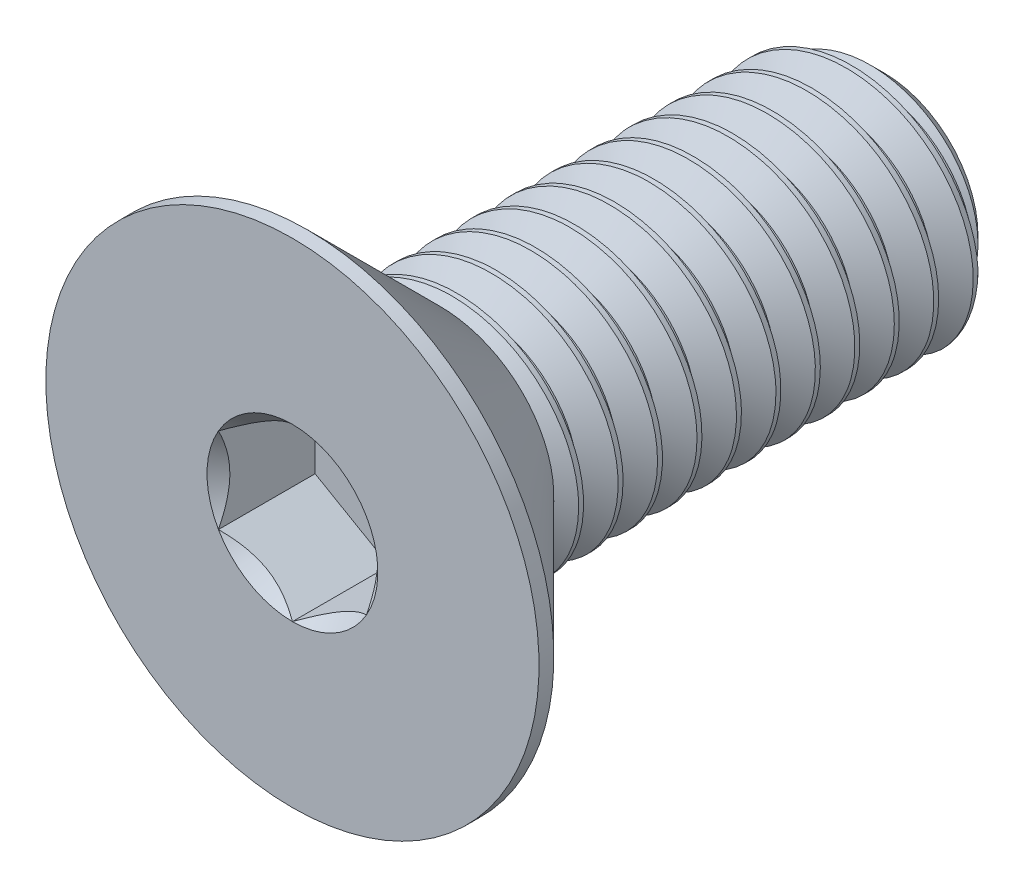
SolidWorks part; units mm, degrees
ref_plane "Front" through (0, 0, 0) normal (0, 0, 1) x (1, 0, 0)
ref_plane "Top" through (0, 0, 0) normal (0, 1, 0) x (1, 0, 0)
ref_plane "Right" through (0, 0, 0) normal (1, 0, 0) x (0, 0, -1)
sketch "Body Sketch" plane through (0, 0, 0) normal (1, 0, 0) x (0, 0, -1)
  line L0 (0, 5) -> (0.3, 5) construction
  line L1 (0.3, 5) -> (2.8, 2.5) construction
  line L2 (0, 2.5) -> (12, 2.5)
  line L3 (12, 2.5) -> (12, 0)
  line L4 (12, 0) -> (0, 0)
  line L5 (0, 0) -> (0, 5) construction
  line L6 (0, 5) -> (0, -5) construction
  line L7 (12, 2.5) -> (12, -2.5) construction
  line L8 (0, -5) -> (0.3, -5) construction
  line L9 (0.3, -5) -> (2.8, -2.5) construction
  line L11 (0, 2.5) -> (0, 0)
  line L12 (2.8, 2.5) -> (2.8, 0) construction
revolve "Body Revolve" add sketch "Body Sketch" angle 360 mid plane about L4
sketch "Thread Spiral Sketch" plane through (0, 0, -12) normal (0, 0, -1) x (-1, 0, 0)
  circle A0 centre (0, 0) radius 2.5
curve "Thread Spiral" pitch 0.8 height 12 radius 2.5 centre (0, 0, -12) axis (0, 0, 1) start towards (0, 1, 0)
sketch "Thread Cut Sketch" plane through (0, 0, 0) normal (1, 0, 0) x (0, 0, -1)
  line L0 (12, 2.5) -> (12.7, 2.5)
  line L1 (12.7, 2.5) -> (12.4, 1.9804)
  line L2 (12.4, 1.9804) -> (12.3, 1.9804)
  line L3 (12.3, 1.9804) -> (12, 2.5)
  line L4 (12.15, 2.2402) -> (12.55, 2.2402) construction
  dimension "D1" = 60
  dimension "D2" = 0.1
  dimension "D3" = 0.4
chamfer "Tip Chamfer" distance 0.6 angle 45 1 edges at (0, 2.5, -12)
sweep "Thread Cut" cut profiles "Thread Cut Sketch" path "Thread Spiral" align with end faces yes
sketch "Head Revolve Sketch" plane through (0, 0, 0) normal (1, 0, 0) x (0, 0, -1)
  line L0 (0, 5) -> (0.3, 5) construction
  line L1 (0.3, 5) -> (2.8, 2.5) construction
  line L2 (0, 5) -> (0.3, 5)
  line L3 (0.3, 5) -> (2.8, 2.5)
  line L4 (2.8, 2.5) -> (2.8, 0) construction
  line L5 (2.8, 2.5) -> (2.8, 0)
  line L7 (0, 0) -> (0, 5) construction
  line L8 (0, 0) -> (0, 5)
  line L9 (0, 0) -> (2.8, 0)
  line L10 (5.5, 0) -> (-5.5, 0) construction
revolve "Head Revolve" add sketch "Head Revolve Sketch" angle 360 mid plane about L9
ref_plane "Base of Head Plane" through (0, 0, -2.8) normal (0, 0, 1) x (1, 0, 0)
sketch "Head to Thread Merger Sketch" plane through (0, 0, -2.8) normal (0, 0, 1) x (1, 0, 0)
  circle A0 centre (0, 0) radius 2.5
extrude "Head to Thread Merger Extrude" add sketch "Head to Thread Merger Sketch" against normal through all draft 45
sketch "Hex Cut Sketch" plane through (0, 0, 0) normal (0, 0, 1) x (1, 0, 0)
  line L1 (1.5, -0.866) -> (1.5, 0.866)
  line L2 (1.5, 0.866) -> (0, 1.7321)
  line L3 (0, 1.7321) -> (-1.5, 0.866)
  line L4 (-1.5, 0.866) -> (-1.5, -0.866)
  line L5 (-1.5, -0.866) -> (0, -1.7321)
  line L6 (0, -1.7321) -> (1.5, -0.866)
  circle A0 centre (0, 0) radius 1.5 construction
  dimension "Hex" = 3
extrude "Hex Cut" cut sketch "Hex Cut Sketch" against normal blind 1.96
sketch "Hex Chamfer Sketch" plane through (0, 0, 0) normal (0, 0, 1) x (1, 0, 0)
  circle A0 centre (0, 0) radius 1.7321
extrude "Hex Chamfer Extrude" cut sketch "Hex Chamfer Sketch" against normal blind 1.96 draft 45
equation "\"D3@Thread Spiral\" = \"Length@Body Sketch\""
equation "\"D2@Thread Cut Sketch\" = \"D4@Thread Spiral\" * .125"
equation "\"D3@Thread Cut Sketch\" = \"D4@Thread Spiral\" * .5"
equation "\"D1@Tip Chamfer\" = \"D4@Thread Spiral\" * .75"
equation "\"D1@Hex Cut\" = \"Head Ht@Body Sketch\" * .7"
equation "\"D1@Hex Chamfer Extrude\" = \"D1@Hex Cut\""
